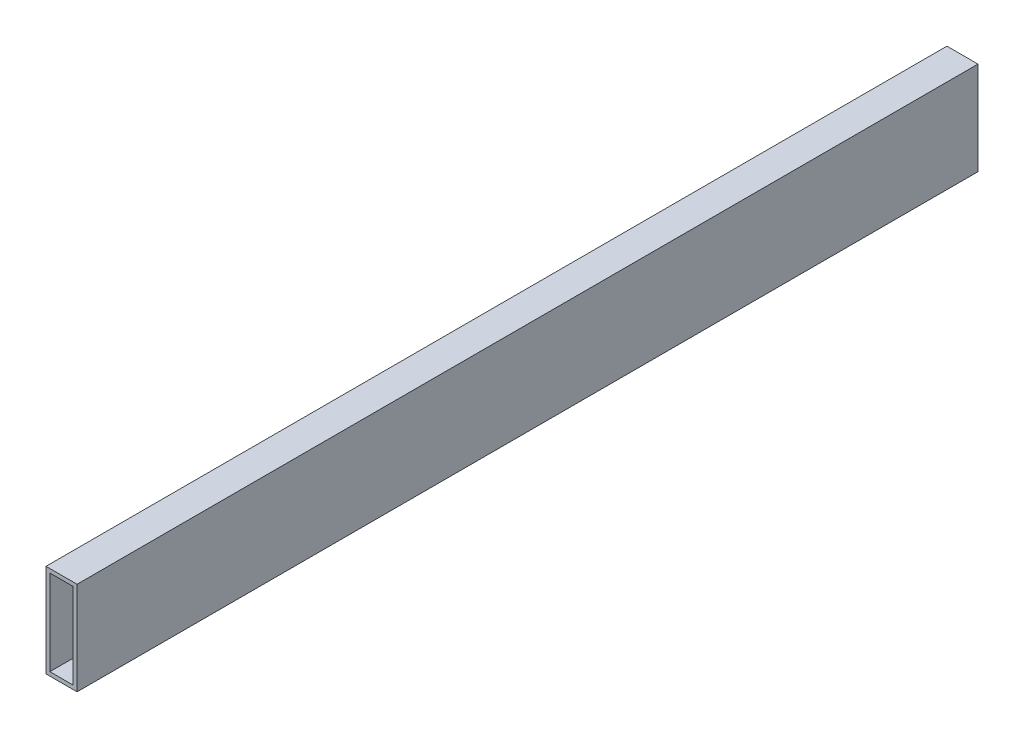
SolidWorks part; units mm, degrees
ref_plane "Front Plane" through (0, 0, 0) normal (0, 0, 1) x (1, 0, 0)
ref_plane "Top Plane" through (0, 0, 0) normal (0, 1, 0) x (1, 0, 0)
ref_plane "Right Plane" through (0, 0, 0) normal (1, 0, 0) x (0, 0, -1)
sketch "Sketch1" plane through (0, 0, 0) normal (0, 0, 1) x (1, 0, 0)
  line L1 (-12.7, -38.1) -> (12.7, -38.1)
  line L2 (-12.7, -38.1) -> (-12.7, 38.1)
  line L3 (-12.7, 38.1) -> (12.7, 38.1)
  line L4 (12.7, -38.1) -> (12.7, 38.1)
  line L5 (-12.7, -38.1) -> (12.7, 38.1) construction
  line L6 (-12.7, 38.1) -> (12.7, -38.1) construction
  point P0 (0, 0)
  dimension "D1" = 25.4
  dimension "D2" = 76.2
extrude "Boss-Extrude1" add sketch "Sketch1" along normal mid plane 736.6
shell "Shell1" thickness 3.175 removed face at (0, 0, -368.3) removed face at (0, 0, 368.3)
